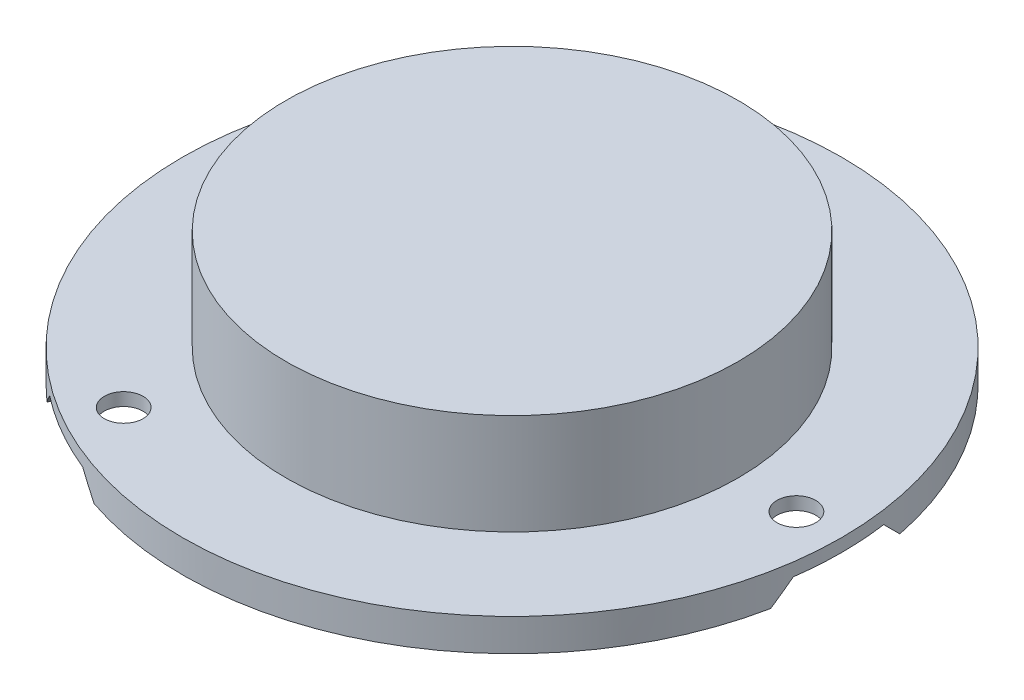
SolidWorks part; units mm, degrees
ref_plane "Front" through (0, 0, 0) normal (0, 0, 1) x (1, 0, 0)
ref_plane "Top" through (0, 0, 0) normal (0, 1, 0) x (1, 0, 0)
ref_plane "Right" through (0, 0, 0) normal (1, 0, 0) x (0, 0, -1)
sketch "Sketch1" plane through (0, 0, 0) normal (0, 0, 1) x (1, 0, 0)
  line L0 (16, 0) -> (25.5, 0)
  line L1 (25.5, 0) -> (25.5, 2.5)
  line L2 (25.5, 2.5) -> (17.5, 2.5)
  line L3 (0, 2.5) -> (0, 0)
  line L4 (0, 2.5) -> (0, 10.3)
  line L5 (0, 10.3) -> (17.5, 10.3)
  line L6 (17.5, 10.3) -> (17.5, 2.5)
  line L7 (0, 0) -> (0, -0.8)
  line L8 (12.5, -0.8) -> (16, -0.8)
  line L9 (16, -0.8) -> (16, 0)
  line L10 (0, -0.8) -> (0, -6.4)
  line L11 (7.5, -6.4) -> (12.5, -6.4)
  line L12 (0, -6.4) -> (0, -8.4)
  line L13 (2, -8.9) -> (7.5, -8.9)
  line L14 (7.5, -8.9) -> (7.5, -6.4)
  line L15 (12.5, -6.4) -> (12.5, -0.8)
  line L17 (0.75, -9.15) -> (2, -9.15)
  line L18 (2, -9.15) -> (2, -8.9)
  arc A0 (0, -8.4) -> (0.75, -9.15) centre (0, -9.15) cw
  dimension "D13" = 0.75
  dimension "D1" = 25.5
  dimension "D2" = 16
  dimension "D3" = 17.5
  dimension "D4" = 7.8
  dimension "D5" = 10.3
  dimension "D6" = 0.8
  dimension "D7" = 12.5
  dimension "D8" = 5.6
  dimension "D11" = 2
revolve "Revolve1" add sketch "Sketch1" angle 360 about L4
hole_wizard "Ø3.0mm Dowel Hole1" positions "Sketch2" profile "Sketch3" hole size "Ø3.0" standard "DIN" end condition through all
sketch "Sketch2" plane through (0, 0, 0) normal (0, -1, 0) x (-1, 0, 0)
  circle A0 centre (0, 0) radius 25.5 construction
  point P0 (-22, 0)
  dimension "D1" = 22
sketch "Sketch3" plane through (22, 0, 0) normal (1, 0, 0) x (0, 0, -1)
  line L0 (0, 0) -> (0, 10.3)
  line L1 (0, 10.3) -> (1.5, 10.3)
  line L2 (1.5, 10.3) -> (1.5, 0)
  line L5 (1.5, 0) -> (0, 0)
  line L11 (0, -6.35) -> (0, 107.95) construction
  dimension "Thru Hole Dia." = 3
  dimension "Thru Hole Depth" = 10.3
sketch "Sketch4" plane through (0, 0, 0) normal (0, 0, 1) x (1, 0, 0)
  line L0 (0, 0) -> (0, -22.242)
sketch "Sketch5" plane through (0, 0, 0) normal (0, -1, 0) x (1, 0, 0)
  line L1 (22, -3.5) -> (25.5, -3.5)
  line L2 (22, 3.5) -> (25.5, 3.5)
  line L3 (25.5, 3.5) -> (25.5, -3.5)
  arc A1 (22, 3.5) -> (22, -3.5) centre (22, 0) ccw
extrude "Cut-Extrude1" cut sketch "Sketch5" against normal blind 1.5
chamfer "Chamfer1" distance 1.5 angle 45 3 edges at (23.6293, 0, -3.5) (18.5, 0, 0) (23.6293, 0, 3.5)
pattern_circular "CirPattern1" count 3 every 120 about axis through (0, 0, 0) along (0, -1, 0) of "Ø3.0mm Dowel Hole1", "Cut-Extrude1", "Chamfer1" reverse direction yes
hole_wizard "M2 Tapped Hole1" positions "Sketch6" profile "Sketch7" tap size "M2" standard "DIN"
sketch "Sketch6" plane through (0, -6.4, 0) normal (0, -1, 0) x (-1, 0, 0)
  point P0 (-10, 0)
  dimension "D1" = 10
sketch "Sketch7" plane through (10, -6.4, 0) normal (1, 0, 0) x (0, 0, -1)
  line L0 (0, 0) -> (0, 5.4807)
  line L1 (0, 5.4807) -> (0.8, 5)
  line L2 (0.8, 5) -> (0.8, 0)
  line L5 (0.8, 0) -> (0, 0)
  line L10 (0, 5.4807) -> (-0.8, 5) construction
  line L11 (0, -6.35) -> (0, 107.95) construction
  dimension "Tap Drill Dia." = 1.6
  dimension "Tap Drill Depth" = 5
  dimension "Drill Angle" = 118
cosmetic thread "Hole Thread1" parameters "D1"=4, "D2"=2
pattern_circular "CirPattern2" count 8 every 45 about axis through (0, 0, 0) along (0, -1, 0) of "M2 Tapped Hole1"
cosmetic thread "Hole Thread2" parameters "D1"=4, "D2"=2
cosmetic thread "Hole Thread3" parameters "D1"=4, "D2"=2
cosmetic thread "Hole Thread4" parameters "D1"=4, "D2"=2
cosmetic thread "Hole Thread5" parameters "D1"=4, "D2"=2
cosmetic thread "Hole Thread6" parameters "D1"=4, "D2"=2
cosmetic thread "Hole Thread7" parameters "D1"=4, "D2"=2
cosmetic thread "Hole Thread8" parameters "D1"=4, "D2"=2
